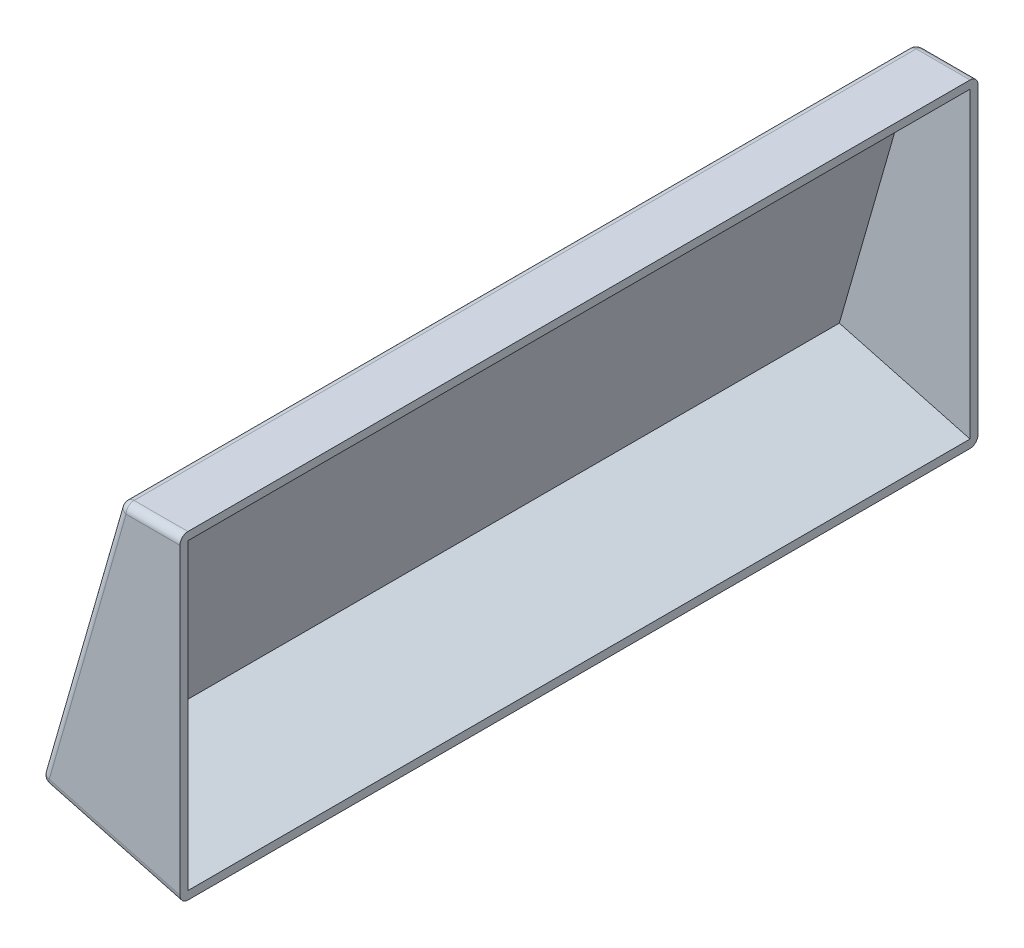
SolidWorks part; units mm, degrees
ref_plane "Front Plane" through (0, 0, 0) normal (0, 0, 1) x (1, 0, 0)
ref_plane "Top Plane" through (0, 0, 0) normal (0, 1, 0) x (1, 0, 0)
ref_plane "Right Plane" through (0, 0, 0) normal (1, 0, 0) x (0, 0, -1)
ref_plane "Plane1" through (-14.4001, 24.845, -6.9362) normal (1, 0, 0) x (0, 0, -1)
sketch "Sketch5" plane through (0, 0, 0) normal (0, 0, 1) x (1, 0, 0)
  line L0 (-20, -17.4069) -> (-20, 62.5931)
  line L1 (-20, 62.5931) -> (-35, 62.5931)
  line L2 (-35, 62.5931) -> (-55.2326, -7.9664)
  line L3 (-55.2326, -7.9664) -> (-20, -17.4069)
  dimension "D1" = 15
  dimension "D2" = 75
  dimension "D3" = 89
sketch "Sketch6" plane through (0, 62.5931, 0) normal (0, 1, 0) x (1, 0, 0)
  line L0 (-20, 0) -> (-20, 200)
  line L1 (-55.2326, 0) -> (-20, 0) construction
sweep "Sweep2" add profiles "Sketch5" path "Sketch6"
fillet "Fillet2" radius 2 8 edges at (-35, 62.5931, -100) (-45.1163, 27.3134, 0) (-55.2326, -7.9664, -100) (-45.1163, 27.3134, -200) (-37.6163, -12.6866, -200) (-27.5, 62.5931, -200) (-37.6163, -12.6866, 0) (-27.5, 62.5931, 0)
shell "Shell2" thickness 2 removed face at (-20, 22.6071, -100)
